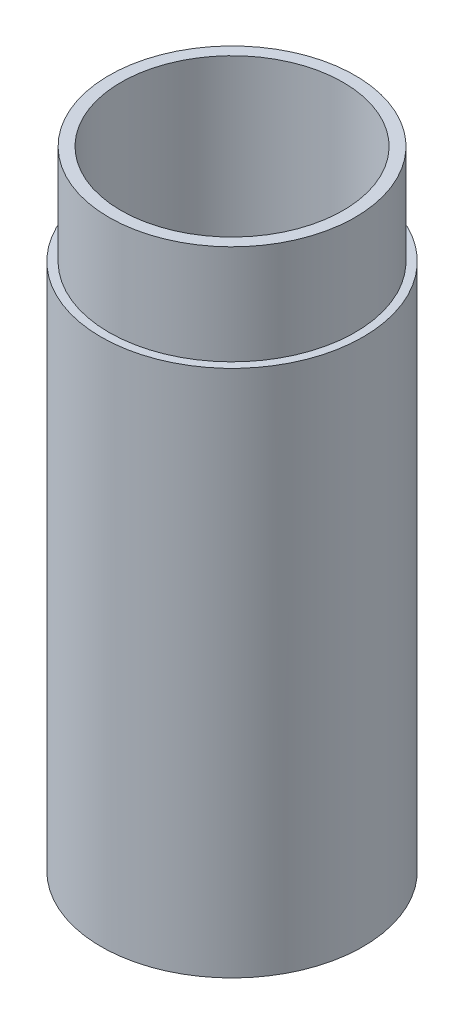
SolidWorks part; units mm, degrees
ref_plane "Front" through (0, 0, 0) normal (0, 0, 1) x (1, 0, 0)
ref_plane "Top" through (0, 0, 0) normal (0, 1, 0) x (1, 0, 0)
ref_plane "Right" through (0, 0, 0) normal (1, 0, 0) x (0, 0, -1)
sketch "Sketch1" plane through (0, 0, 0) normal (0, 1, 0) x (1, 0, 0)
  circle A0 centre (0, 0) radius 11.15
  circle A1 centre (0, 0) radius 13.15
  dimension "D1" = 22.3
  dimension "D2" = 2
extrude "Boss-Extrude1" add sketch "Sketch1" along normal blind 60
sketch "Sketch2" plane through (0, 0, 0) normal (0, -1, 0) x (1, 0, 0)
  circle A0 centre (0, 0) radius 9.15
  circle A1 centre (0, 0) radius 13.15
  circle A2 centre (0, 0) radius 13.15
  dimension "D1" = 0
  dimension "D2" = 4
extrude "Boss-Extrude2" add sketch "Sketch2" along normal blind 3
sketch "Sketch3" plane through (0, 60, 0) normal (0, 1, 0) x (1, 0, 0)
  circle A0 centre (0, 0) radius 13.15 construction
  circle A1 centre (0, 0) radius 13.15
  circle A2 centre (0, 0) radius 12.35
  dimension "D1" = 0.8
extrude "Cut-Extrude1" cut sketch "Sketch3" against normal blind 10
